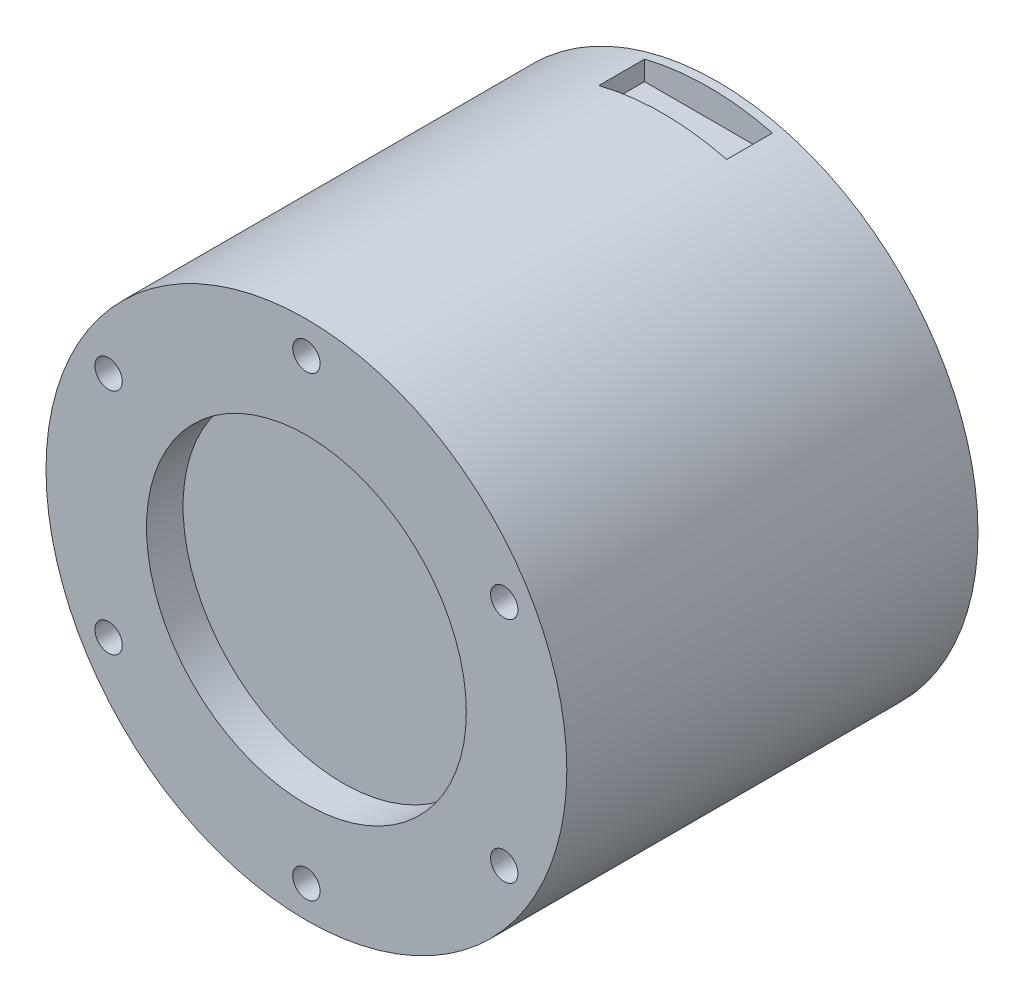
SolidWorks part; units mm, degrees
ref_plane "前视基准面" through (0, 0, 0) normal (0, 0, 1) x (1, 0, 0)
ref_plane "上视基准面" through (0, 0, 0) normal (0, 1, 0) x (1, 0, 0)
ref_plane "右视基准面" through (0, 0, 0) normal (1, 0, 0) x (0, 0, -1)
sketch "草图1" plane through (0, 0, 0) normal (0, 0, 1) x (1, 0, 0)
  circle A0 centre (0, 0) radius 28.5
  dimension "D1" = 57
extrude "凸台-拉伸1" add sketch "草图1" along normal blind 45
sketch "草图2" plane through (0, 0, 45) normal (0, 0, 1) x (1, 0, 0)
  circle A0 centre (0, 0) radius 17.5
  circle A1 centre (0, 0) radius 25
  circle A2 centre (0, 25) radius 1.5
  circle A3 centre (21.6506, 12.5) radius 1.5
  circle A4 centre (21.6506, -12.5) radius 1.5
  circle A5 centre (0, -25) radius 1.5
  circle A6 centre (-21.6506, -12.5) radius 1.5
  circle A7 centre (-21.6506, 12.5) radius 1.5
  point P18 (0, 0)
  dimension "D1" = 35
  dimension "D2" = 50
  dimension "D3" = 3
  dimension "D4" = 6
extrude "切除-拉伸2" cut sketch "草图2" against normal blind 4 contours A0 region at (0, 0, 45)
extrude "切除-拉伸3" cut sketch "草图2<5>" against normal blind 5 contours A2 | A3 | A4 | A5 | A6 | A7
sketch "草图2<5>" plane through (0, 0, 45) normal (0, 0, 1) x (1, 0, 0) same geometry as "草图2"
sketch "草图4" plane through (0, 0, 0) normal (0, 0, -1) x (-1, 0, 0)
  line L0 (0, 0) -> (0, 28.5) construction
  line L1 (0, 0) -> (-13.435, 13.435)
  circle A0 centre (0, 0) radius 19
  circle A7 centre (13.435, 13.435) radius 1.5
  circle A8 centre (-13.435, 13.435) radius 1.5
  circle A9 centre (13.435, -13.435) radius 1.5
  circle A10 centre (-13.435, -13.435) radius 1.5
  point P16 (0, 0)
  point P18 (0, 0)
  dimension "D1" = 38
  dimension "D2" = 45
  dimension "D3" = 3
  dimension "D4" = 4
extrude "切除-拉伸4" cut sketch "草图4" against normal blind 4 contours A8 | A7 | A9 | A10
sketch "草图8" plane through (0, 0, 0) normal (0, 1, 0) x (1, 0, 0)
  line L0 (0, 0) -> (0, -41) construction
  line L3 (-7, -1) -> (-7, -6)
  line L5 (-7, -6) -> (7, -6)
  line L6 (7, -6) -> (7, -1)
  line L7 (-7, -1) -> (7, -1)
  line L8 (28.5, 0) -> (-28.5, 0) construction
  point P5 (0, -1)
  dimension "D1" = 14
  dimension "D2" = 5
  dimension "D3" = 1
ref_plane "基准面1" through (0, 28.5, 0) normal (0, 1, 0) x (1, 0, 0)
sketch "草图9" plane through (0, 28.5, 0) normal (0, 1, 0) x (1, 0, 0)
  line L0 (-7, -1) -> (-7, -6)
  line L1 (-7, -6) -> (7, -6)
  line L2 (7, -6) -> (7, -1)
  line L3 (-7, -1) -> (7, -1)
  line L4 (0, 200000) -> (0, -200041) construction
  line L5 (28.5, 0) -> (-28.5, 0) construction
  point P2 (0, -1)
  dimension "D1" = 14
  dimension "D2" = 5
  dimension "D3" = 1
extrude "切除-拉伸6" cut sketch "草图9" against normal blind 3
mirror "镜向1" about plane through (0, 0, 0) normal (0, 1, 0) of "切除-拉伸6"
ref_plane "基准面2" through (-28.5, 0, 0) normal (1, 0, 0) x (0, 0, -1)
sketch "草图10" plane through (-28.5, 0, 0) normal (1, 0, 0) x (0, 0, -1)
  line L0 (-1, 4) -> (-1, -4)
  line L1 (-1, 4) -> (-9, 4)
  line L2 (-9, 4) -> (-9, -4)
  line L3 (-9, -4) -> (-1, -4)
  line L4 (0, -28.5) -> (0, 28.5) construction
  line L6 (-43.3986, 0) -> (5.7011, 0) construction
  point P6 (-1, 0)
  dimension "D1" = 8
  dimension "D2" = 8
  dimension "D3" = 1
extrude "切除-拉伸7" cut sketch "草图10" along normal blind 3
